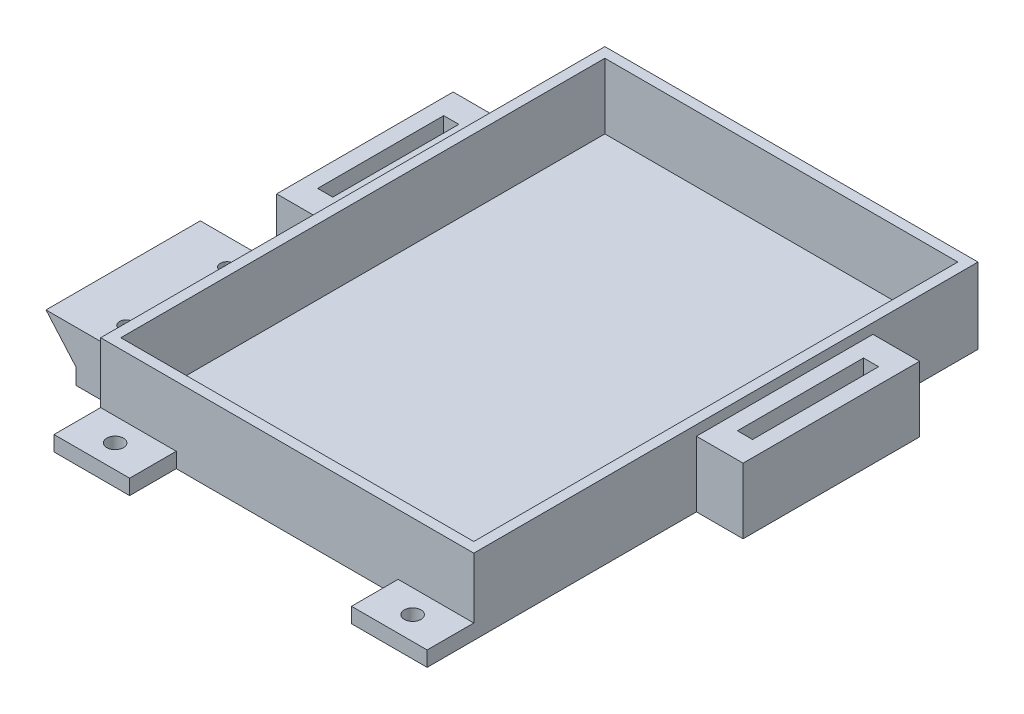
SolidWorks part; units mm, degrees
ref_plane "Front Plane" through (0, 0, 0) normal (0, 0, 1) x (1, 0, 0)
ref_plane "Top Plane" through (0, 0, 0) normal (0, 1, 0) x (1, 0, 0)
ref_plane "Right Plane" through (0, 0, 0) normal (1, 0, 0) x (0, 0, -1)
sketch "Sketch2" plane through (0, 0, 0) normal (0, 1, 0) x (1, 0, 0)
  line L1 (0, 123) -> (92.5, 123) construction
  line L2 (0, 123) -> (0, 0) construction
  line L3 (0, 0) -> (92.5, 0) construction
  line L4 (92.5, 123) -> (92.5, 0) construction
  line L5 (9.25, 115) -> (83.25, 115)
  line L6 (9.25, 100) -> (9.25, 15)
  line L7 (24.25, 15) -> (68.25, 15)
  line L8 (83.25, 115) -> (83.25, 15)
  line L10 (4.625, 115) -> (4.625, 100) construction
  line L11 (9.25, 115) -> (0, 115)
  line L13 (9.25, 100) -> (0, 100)
  line L14 (0, 115) -> (0, 100)
  line L15 (0, 107.5) -> (9.25, 107.5) construction
  line L16 (9.25, 10.375) -> (24.25, 10.375) construction
  line L17 (9.25, 15) -> (9.25, 5.75)
  line L18 (24.25, 15) -> (24.25, 5.75)
  line L19 (9.25, 5.75) -> (24.25, 5.75)
  line L20 (68.25, 10.375) -> (83.25, 10.375) construction
  line L21 (68.25, 15) -> (68.25, 5.75)
  line L22 (83.25, 15) -> (83.25, 5.75)
  line L23 (68.25, 5.75) -> (83.25, 5.75)
  line L24 (9.25, 15) -> (24.25, 15)
  line L25 (68.25, 15) -> (83.25, 15)
  line L26 (9.25, 100) -> (9.25, 115)
  circle A0 centre (4.625, 107.5) radius 1.65
  circle A1 centre (16.75, 10.375) radius 1.65
  circle A2 centre (75.75, 10.375) radius 1.65
  dimension "D8" = 3.3
  dimension "D9" = 9.25
  dimension "D12" = 3.3
  dimension "D15" = 3.3
  dimension "D1" = 92.5
  dimension "D2" = 8
  dimension "D3" = 100
  dimension "D4" = 9.25
  dimension "D5" = 74
  dimension "D6" = 15
  dimension "D7" = 15
  dimension "D10" = 9.25
  dimension "D11" = 15
  dimension "D13" = 9.25
  dimension "D14" = 15
extrude "Boss-Extrude1" add sketch "Sketch2" along normal blind 15 contours L26 L6 L24 L7 L25 L8 L5 region at (46.25, 0, -65)
extrude "Boss-Extrude2" add sketch "Sketch2<3>" along normal blind 3 contours L13 L26 L11 L14 A0 | L24 L17 L19 L18 A1 | L25 L21 L23 L22 A2 region at (9.0738, 0, -107.5) region at (83.0738, 0, -10.375) region at (16.75, 0, -14.8238)
sketch "Sketch2<3>" plane through (0, 0, 0) normal (0, 1, 0) x (1, 0, 0) same geometry as "Sketch2"
sketch "Sketch3" plane through (0, 15, 0) normal (0, 1, 0) x (1, 0, 0)
  line L1 (11.25, 113) -> (81.25, 113)
  line L2 (11.25, 113) -> (11.25, 17)
  line L3 (11.25, 17) -> (81.25, 17)
  line L4 (81.25, 113) -> (81.25, 17)
extrude "Cut-Extrude1" cut sketch "Sketch3" against normal blind 13 contours L1 L4 L3 L2
sketch "Sketch5" plane through (0, 0, 0) normal (0, 1, 0) x (1, 0, 0)
  line L0 (9.25, 15) -> (9.25, 115) construction
  line L1 (9.25, 49.958) -> (0, 49.958)
  line L2 (9.25, 49.958) -> (9.25, 19.358)
  line L3 (9.25, 19.358) -> (0, 19.358)
  line L4 (0, 49.958) -> (0, 19.358)
  line L5 (0, 115) -> (0, 100) construction
  line L6 (0, 34.658) -> (9.25, 34.658) construction
  line L7 (4.625, 19.358) -> (4.625, 24.658) construction
  circle A0 centre (4.625, 44.658) radius 1.3
  circle A1 centre (4.625, 24.658) radius 1.3
  dimension "D1" = 2.6
  dimension "D3" = 5.3
  dimension "D2" = 20
extrude "Boss-Extrude4" add sketch "Sketch5" along normal blind 10
sketch "Sketch6" plane through (0, 0, -49.958) normal (0, 0, -1) x (-1, 0, 0)
  line L0 (0, 3.1777) -> (5.9425, 10)
  line L1 (0, 0) -> (0, 10) construction
  line L2 (5.9425, 10) -> (0, 10)
  line L4 (0, 10) -> (0, 3.1777)
  line L14 (-9.25, 10) -> (0, 10) construction
extrude "Boss-Extrude5" add sketch "Sketch6" against normal up to surface (30.6 mm away) up to face at (4.625, 5, -19.358)
sketch "Sketch9" plane through (0, 0, 0) normal (0, -1, 0) x (1, 0, 0)
  line L0 (0, -115) -> (0, -100) construction
  line L1 (0, -94.1615) -> (9.25, -94.1615)
  line L2 (0, -94.1615) -> (0, -59.1615)
  line L3 (0, -59.1615) -> (9.25, -59.1615)
  line L4 (9.25, -94.1615) -> (9.25, -59.1615)
  line L5 (0, -94.1615) -> (9.25, -59.1615) construction
  line L6 (0, -59.1615) -> (9.25, -94.1615) construction
  line L7 (9.25, -49.958) -> (9.25, -100) construction
  line L9 (6.125, -89.1615) -> (3.125, -89.1615)
  line L10 (6.125, -89.1615) -> (6.125, -64.1615)
  line L11 (6.125, -64.1615) -> (3.125, -64.1615)
  line L12 (3.125, -89.1615) -> (3.125, -64.1615)
  line L13 (6.125, -89.1615) -> (3.125, -64.1615) construction
  line L14 (6.125, -64.1615) -> (3.125, -89.1615) construction
  point P0 (4.625, -76.6615)
  point P9 (4.625, -76.6615)
  dimension "D1" = 3
  dimension "D2" = 5
  dimension "D3" = 35
extrude "Boss-Extrude6" add sketch "Sketch9" against normal blind 3 contours L2 L3 L4 L1
extrude "Boss-Extrude7" add sketch "Sketch9<4>" against normal blind 13
sketch "Sketch9<4>" plane through (0, 0, 0) normal (0, -1, 0) x (1, 0, 0) same geometry as "Sketch9"
ref_plane "Plane2" through (46.25, 0, 0) normal (-1, 0, 0) x (0, 0, 1)
mirror "Mirror1" about plane through (46.25, 0, 0) normal (-1, 0, 0) of "Boss-Extrude7", "Boss-Extrude6"
